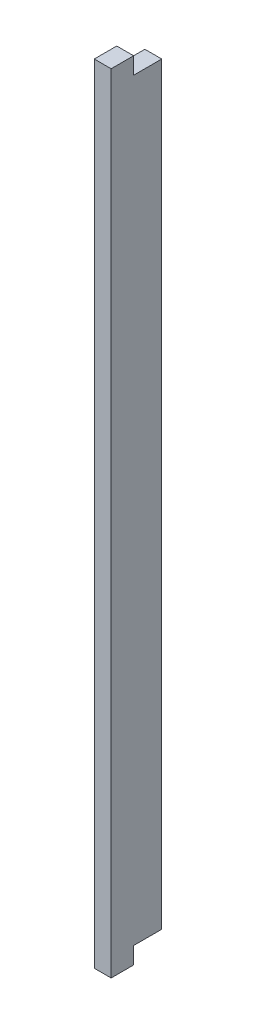
SolidWorks part; units mm, degrees
ref_plane "Front Plane" through (0, 0, 0) normal (0, 0, 1) x (1, 0, 0)
ref_plane "Top Plane" through (0, 0, 0) normal (0, 1, 0) x (1, 0, 0)
ref_plane "Right Plane" through (0, 0, 0) normal (1, 0, 0) x (0, 0, -1)
sketch "Sketch1" plane through (0, 0, 0) normal (1, 0, 0) x (0, 0, -1)
  line L1 (-4.5, -30.8442) -> (0, -30.8442)
  line L2 (-4.5, -30.8442) -> (-4.5, 39.1558)
  line L3 (-4.5, 39.1558) -> (0, 39.1558)
  line L4 (0, -30.8442) -> (0, 39.1558)
  point P4 (0, 0)
  dimension "D1" = 70
  dimension "D2" = 4.5
extrude "Boss-Extrude1" add sketch "Sketch1" along normal blind 1.5
sketch "Sketch3" plane through (1.5, 0, 0) normal (1, 0, 0) x (0, 0, -1)
  line L0 (-4.5, 39.1558) -> (-4.5, -30.8442) construction
  line L1 (0, 39.1558) -> (-2.5, 39.1558)
  line L2 (0, 39.1558) -> (0, 37.6558)
  line L3 (0, 37.6558) -> (-2.5, 37.6558)
  line L4 (-2.5, 39.1558) -> (-2.5, 37.6558)
  line L5 (0, -30.8442) -> (-2.5, -30.8442)
  line L6 (0, -30.8442) -> (0, -29.3442)
  line L7 (0, -29.3442) -> (-2.5, -29.3442)
  line L8 (-2.5, -30.8442) -> (-2.5, -29.3442)
  dimension "D1" = 1.5
  dimension "D2" = 2
extrude "Cut-Extrude1" cut sketch "Sketch3" against normal blind 2
